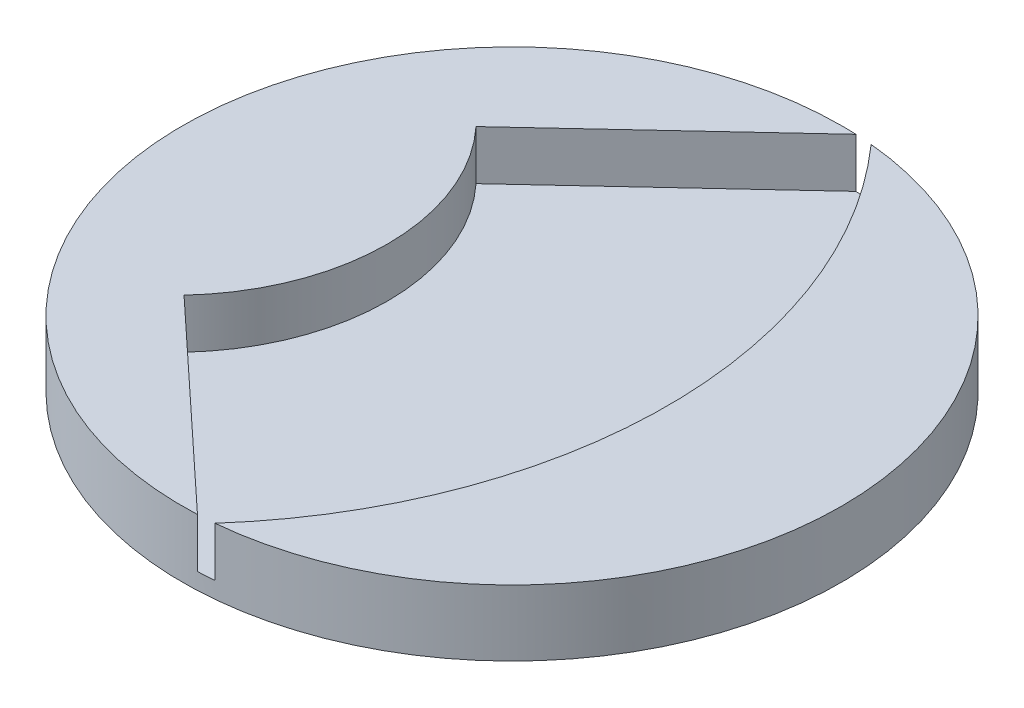
SolidWorks part; units mm, degrees
ref_plane "Front Plane" through (0, 0, 0) normal (0, 0, 1) x (1, 0, 0)
ref_plane "Top Plane" through (0, 0, 0) normal (0, 1, 0) x (1, 0, 0)
ref_plane "Right Plane" through (0, 0, 0) normal (1, 0, 0) x (0, 0, -1)
sketch "Sketch1" plane through (0, 0, 0) normal (0, 0, 1) x (1, 0, 0)
  line L0 (1.15, -2) -> (1.15, 2)
  line L1 (1.15, 2) -> (0, 2)
  line L2 (0, 2) -> (0, 6)
  line L3 (0, 6) -> (20, 6)
  line L4 (20, 6) -> (20, 2)
  line L5 (20, 2) -> (3.15, 2)
  line L6 (3.15, 2) -> (3.15, -2)
  line L7 (3.15, -2) -> (1.15, -2)
  line L8 (0, -3.5392) -> (0, 6.3608) construction
  point P9 (1.15, 0)
  dimension "D1" = 2.3
  dimension "D2" = 2
  dimension "D3" = 4
  dimension "D4" = 4
  dimension "D5" = 40
revolve "Revolve1" add sketch "Sketch1" angle 360 about L8
sketch "Sketch2" plane through (0, 6, 0) normal (0, 1, 0) x (1, 0, 0)
  line L0 (1.3923, 20.4492) -> (-11.0464, 8.8613)
  line L1 (1.3923, -20.4492) -> (-11.0464, -8.8613)
  line L2 (9.4416, 0) -> (-7.5584, 0) construction
  arc A0 (1.3923, 20.4492) -> (1.3923, -20.4492) centre (-20.5584, 0) cw
  arc A1 (-11.0464, 8.8613) -> (-11.0464, -8.8613) centre (-20.5584, 0) cw
  dimension "IR" = 13
  dimension "OR" = 30
  dimension "D1" = 20.5584
extrude "Cut-Extrude1" cut sketch "Sketch2" against normal blind 3
equation "\"D1@Sketch2\"=2*(\"OR@Sketch2\"^3-\"IR@Sketch2\"^3)*sin(\"a@Sketch2\")/(3*\"a@Sketch2\"*(\"OR@Sketch2\"^2-\"IR@Sketch2\"^2))"
